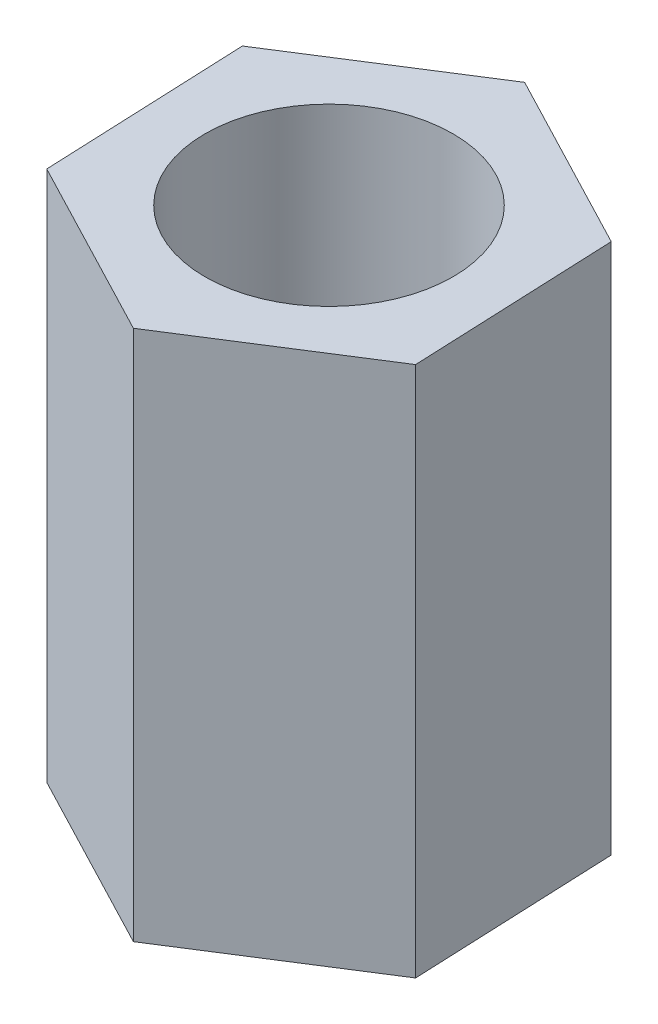
SolidWorks part; units mm, degrees
ref_plane "前视基准面" through (0, 0, 0) normal (0, 0, 1) x (1, 0, 0)
ref_plane "上视基准面" through (0, 0, 0) normal (0, 1, 0) x (1, 0, 0)
ref_plane "右视基准面" through (0, 0, 0) normal (1, 0, 0) x (0, 0, -1)
other "Configuration Table"
sketch "草图1" plane through (0, 0, 0) normal (0, 1, 0) x (1, 0, 0)
  line L1 (3.0707, -1.6034) -> (2.9239, 1.8576)
  line L2 (2.9239, 1.8576) -> (-0.1468, 3.461)
  line L3 (-0.1468, 3.461) -> (-3.0707, 1.6034)
  line L4 (-3.0707, 1.6034) -> (-2.9239, -1.8576)
  line L5 (-2.9239, -1.8576) -> (0.1468, -3.461)
  line L6 (0.1468, -3.461) -> (3.0707, -1.6034)
  circle A0 centre (0, 0) radius 2.1
  circle A1 centre (0, 0) radius 3 construction
extrude "凸台-拉伸1" add sketch "草图1" along normal blind 60
sketch "草图2" plane through (0, 60, 0) normal (0, 1, 0) x (1, 0, 0)
  line L6 (0.1468, -3.461) -> (3.0707, -1.6034)
  line L7 (3.0707, -1.6034) -> (2.9239, 1.8576)
  line L8 (2.9239, 1.8576) -> (-0.1468, 3.461)
  line L9 (-0.1468, 3.461) -> (-3.0707, 1.6034)
  line L10 (-3.0707, 1.6034) -> (-2.9239, -1.8576)
  line L11 (-2.9239, -1.8576) -> (0.1468, -3.461)
  line L12 (0.1468, -3.461) -> (3.0707, -1.6034)
  line L13 (3.0707, -1.6034) -> (2.9239, 1.8576)
  line L14 (2.9239, 1.8576) -> (-0.1468, 3.461)
  line L15 (-0.1468, 3.461) -> (-3.0707, 1.6034)
  line L16 (-3.0707, 1.6034) -> (-2.9239, -1.8576)
  line L17 (-2.9239, -1.8576) -> (0.1468, -3.461)
  line M7 (0.1468, -3.461) -> (3.0707, -1.6034)
  line M8 (3.0707, -1.6034) -> (2.9239, 1.8576)
  line M9 (2.9239, 1.8576) -> (-0.1468, 3.461)
  line M10 (-0.1468, 3.461) -> (-3.0707, 1.6034)
  line M11 (-3.0707, 1.6034) -> (-2.9239, -1.8576)
  line M12 (-2.9239, -1.8576) -> (0.1468, -3.461)
  circle M13 centre (0, 0) radius 2.1
  dimension "D1" = 0
extrude "凸台-拉伸2" add sketch "草图2" along normal blind 40 contours M12 M7 M8 M9 M10 M11 M13 region at (-1.3457, 60, 2.5773)
sketch "草图3" plane through (0, 100, 0) normal (0, 1, 0) x (1, 0, 0)
  line L6 (-2.9239, -1.8576) -> (0.1468, -3.461)
  line L7 (0.1468, -3.461) -> (3.0707, -1.6034)
  line L8 (3.0707, -1.6034) -> (2.9239, 1.8576)
  line L9 (2.9239, 1.8576) -> (-0.1468, 3.461)
  line L10 (-0.1468, 3.461) -> (-3.0707, 1.6034)
  line L11 (-3.0707, 1.6034) -> (-2.9239, -1.8576)
  line L12 (-2.9239, -1.8576) -> (0.1468, -3.461)
  line L13 (0.1468, -3.461) -> (3.0707, -1.6034)
  line L14 (3.0707, -1.6034) -> (2.9239, 1.8576)
  line L15 (2.9239, 1.8576) -> (-0.1468, 3.461)
  line L16 (-0.1468, 3.461) -> (-3.0707, 1.6034)
  line L17 (-3.0707, 1.6034) -> (-2.9239, -1.8576)
  dimension "D1" = 0
extrude "切除-拉伸1" cut sketch "草图3" against normal blind 95
sketch "草图4" plane through (0, 5, 0) normal (0, 1, 0) x (1, 0, 0)
  line L6 (-3.0707, 1.6034) -> (-2.9239, -1.8576)
  line L7 (-2.9239, -1.8576) -> (0.1468, -3.461)
  line L8 (0.1468, -3.461) -> (3.0707, -1.6034)
  line L9 (3.0707, -1.6034) -> (2.9239, 1.8576)
  line L10 (2.9239, 1.8576) -> (-0.1468, 3.461)
  line L11 (-0.1468, 3.461) -> (-3.0707, 1.6034)
  line L12 (-3.0707, 1.6034) -> (-2.9239, -1.8576)
  line L13 (-2.9239, -1.8576) -> (0.1468, -3.461)
  line L14 (0.1468, -3.461) -> (3.0707, -1.6034)
  line L15 (3.0707, -1.6034) -> (2.9239, 1.8576)
  line L16 (2.9239, 1.8576) -> (-0.1468, 3.461)
  line L17 (-0.1468, 3.461) -> (-3.0707, 1.6034)
  circle M7 centre (0, 0) radius 2.1
  line M8 (-3.0707, 1.6034) -> (-2.9239, -1.8576)
  line M9 (-2.9239, -1.8576) -> (0.1468, -3.461)
  line M10 (0.1468, -3.461) -> (3.0707, -1.6034)
  line M11 (3.0707, -1.6034) -> (2.9239, 1.8576)
  line M12 (2.9239, 1.8576) -> (-0.1468, 3.461)
  line M13 (-0.1468, 3.461) -> (-3.0707, 1.6034)
  dimension "D1" = 0
extrude "凸台-拉伸3" add sketch "草图4" along normal blind 4 contours M13 M8 M9 M10 M11 M12 M7 region at (-1.5591, 5, -2.4541)
